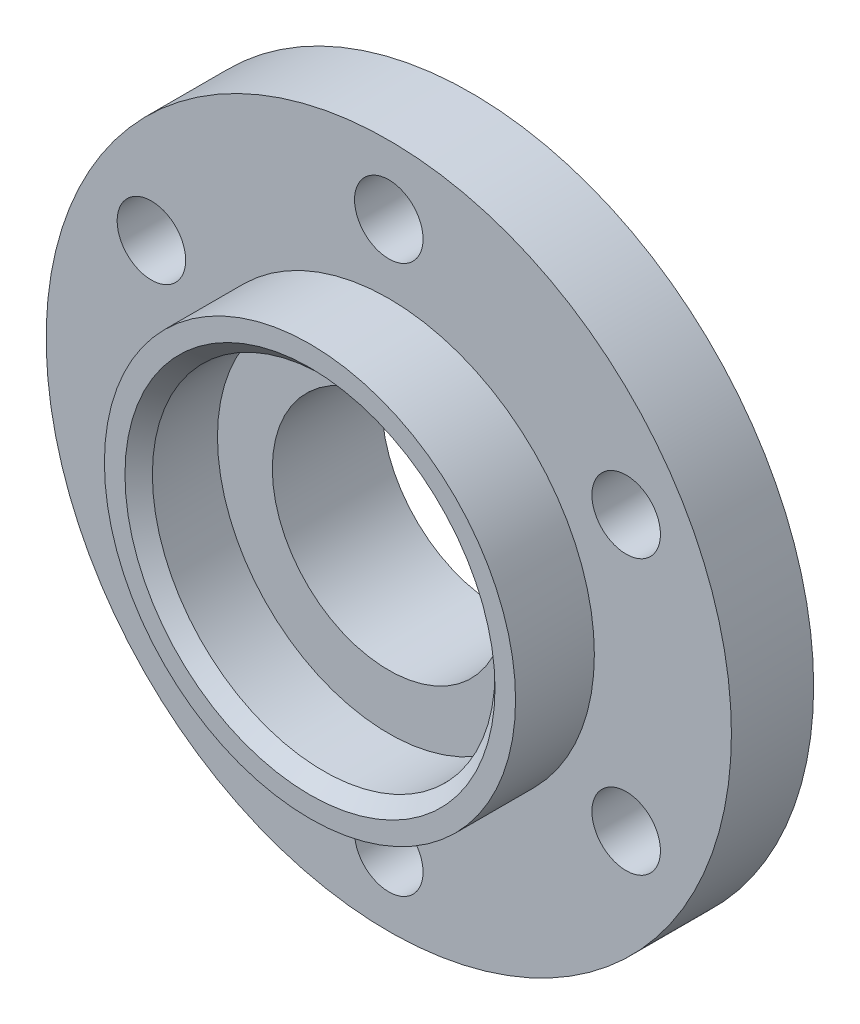
SolidWorks part; units mm, degrees
ref_plane "Front Plane" through (0, 0, 0) normal (0, 0, 1) x (1, 0, 0)
ref_plane "Top Plane" through (0, 0, 0) normal (0, 1, 0) x (1, 0, 0)
ref_plane "Right Plane" through (0, 0, 0) normal (1, 0, 0) x (0, 0, -1)
sketch "Sketch1" plane through (0, 0, 0) normal (0, 0, 1) x (1, 0, 0)
  circle A0 centre (0, 0) radius 25
  dimension "D1" = 50
extrude "Boss-Extrude1" add sketch "Sketch1" along normal blind 6
sketch "Sketch2" plane through (0, 0, 6) normal (0, 0, 1) x (1, 0, 0)
  circle A0 centre (0, 0) radius 15
  circle A1 centre (0, 0) radius 12.5
  dimension "D1" = 30
  dimension "D2" = 25
extrude "Boss-Extrude2" add sketch "Sketch2" along normal blind 5.75
sketch "Sketch3" plane through (0, 0, 0) normal (0, 0, -1) x (-1, 0, 0)
  circle A0 centre (0, 0) radius 14
  dimension "D1" = 28
extrude "Boss-Extrude3" add sketch "Sketch3" along normal blind 2
fillet "Fillet1" radius 2 1 edges at (-14, 0, -2)
chamfer "Chamfer1" distance 1 angle 45 1 edges at (12.5, 0, 11.75)
hole_wizard "Ø5.0 (5) Diameter Hole1" positions "Sketch9" profile "Sketch8" hole size "Ø5.0" standard "ISO" end condition through all
sketch "Sketch9" plane through (0, 0, 0) normal (0, 0, -1) x (-1, 0, 0)
  point P0 (0, 20)
  dimension "D1" = 0
  dimension "D2" = 20
sketch "Sketch8" plane through (0, 20, 0) normal (1, 0, 0) x (0, 1, 0)
  line L0 (0, 0) -> (0, 11.75)
  line L1 (0, 11.75) -> (2.5, 11.75)
  line L2 (2.5, 11.75) -> (2.5, 0)
  line L5 (2.5, 0) -> (0, 0)
  line L11 (0, -6.35) -> (0, 107.95) construction
  dimension "Thru Hole Dia." = 5
  dimension "Thru Hole Depth" = 11.75
pattern_circular "CirPattern1" count 6 over 360 about axis through (0, 0, 6) along (0, 0, -1) of "Ø5.0 (5) Diameter Hole1"
sketch "Sketch10" plane through (0, 0, -2) normal (0, 0, -1) x (-1, 0, 0)
  circle A0 centre (0, 0) radius 8.5
  dimension "D1" = 17
extrude "Cut-Extrude1" cut sketch "Sketch10" against normal through all
